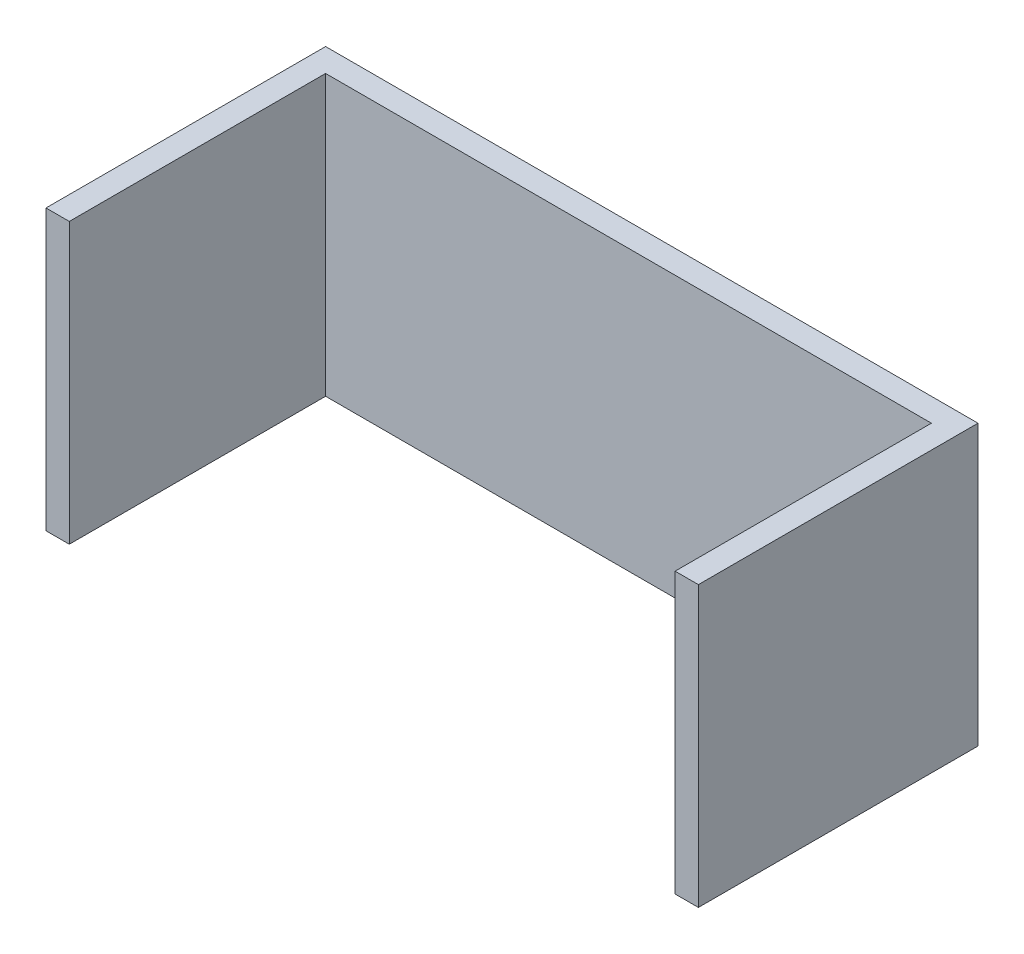
SolidWorks part; units mm, degrees
material "6061 Alloy"
ref_plane "Front Plane" through (0, 0, 0) normal (0, 0, 1) x (1, 0, 0)
ref_plane "Top Plane" through (0, 0, 0) normal (0, 1, 0) x (1, 0, 0)
ref_plane "Right Plane" through (0, 0, 0) normal (1, 0, 0) x (0, 0, -1)
sketch "Sketch1" plane through (0, 0, 0) normal (0, 1, 0) x (1, 0, 0)
  line L1 (-88.9, -38.1) -> (88.9, -38.1)
  line L2 (-88.9, -38.1) -> (-88.9, 38.1)
  line L3 (-88.9, 38.1) -> (88.9, 38.1)
  line L4 (88.9, -38.1) -> (88.9, 38.1)
  line L5 (-88.9, -38.1) -> (88.9, 38.1) construction
  line L6 (-88.9, 38.1) -> (88.9, -38.1) construction
  point P0 (0, 0)
  dimension "D1" = 76.2
  dimension "D2" = 177.8
extrude "Boss-Extrude1" add sketch "Sketch1" along normal blind 76.2
sketch "Sketch3" plane through (0, 76.2, 0) normal (0, 1, 0) x (1, 0, 0)
  line L0 (-88.9, -38.1) -> (88.9, -38.1) construction
  line L1 (-82.55, -38.1) -> (82.55, -38.1)
  line L2 (-82.55, -38.1) -> (-82.55, 31.75)
  line L3 (-82.55, 31.75) -> (82.55, 31.75)
  line L4 (82.55, -38.1) -> (82.55, 31.75)
  line L5 (-88.9, 38.1) -> (-88.9, -38.1) construction
  line L6 (88.9, -38.1) -> (88.9, 38.1) construction
  dimension "D1" = 69.85
  dimension "D2" = 6.35
  dimension "D3" = 6.35
extrude "Cut-Extrude1" cut sketch "Sketch3" against normal through all
